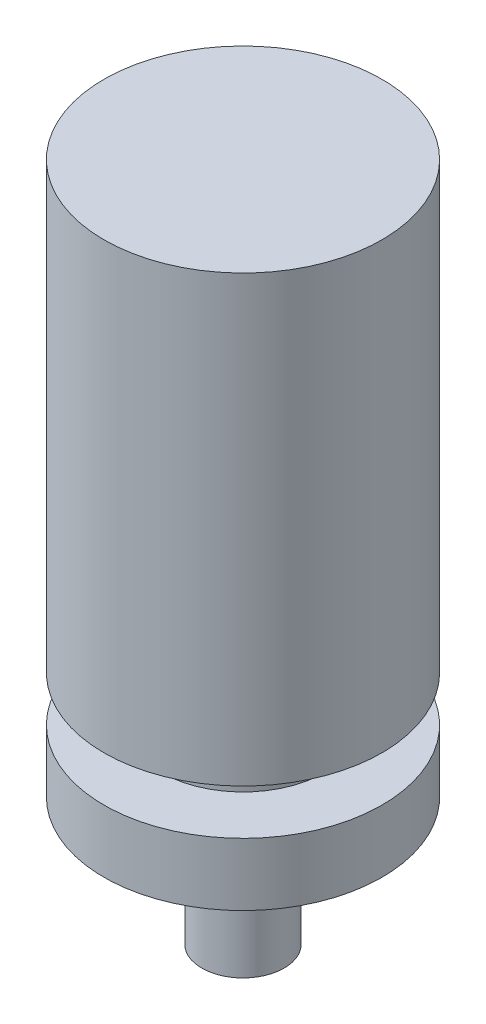
SolidWorks part; units mm, degrees
ref_plane "Front Plane" through (0, 0, 0) normal (0, 0, 1) x (1, 0, 0)
ref_plane "Top Plane" through (0, 0, 0) normal (0, 1, 0) x (1, 0, 0)
ref_plane "Right Plane" through (0, 0, 0) normal (1, 0, 0) x (0, 0, -1)
sketch "Sketch1" plane through (0, 0, 0) normal (0, 1, 0) x (1, 0, 0)
  circle A0 centre (0, 0) radius 16.891
  dimension "D1" = 33.782
extrude "Extrude1" add sketch "Sketch1" along normal blind 7.6
sketch "Sketch2" plane through (0, 7.6, 0) normal (0, 1, 0) x (1, 0, 0)
  circle A0 centre (0, 0) radius 9.9983
extrude "Extrude2" add sketch "Sketch2" along normal blind 5.5
sketch "Sketch3" plane through (0, 13.1, 0) normal (0, 1, 0) x (1, 0, 0)
  circle A0 centre (0, 0) radius 16.891
  dimension "D1" = 33.782
extrude "Extrude3" add sketch "Sketch3" along normal blind 53.975
sketch "Sketch4" plane through (0, 0, 0) normal (0, -1, 0) x (1, 0, 0)
  circle A0 centre (0, 0) radius 5.5
  dimension "D1" = 11
extrude "Boss-Extrude1" add sketch "Sketch4" along normal blind 15.5
sketch "Sketch5" plane through (0, -15.5, 0) normal (0, -1, 0) x (1, 0, 0)
  circle A0 centre (0, 0) radius 5
  circle A1 centre (0, 0) radius 5.5
  dimension "D1" = 10
extrude "Cut-Extrude1" cut sketch "Sketch5" against normal blind 9
